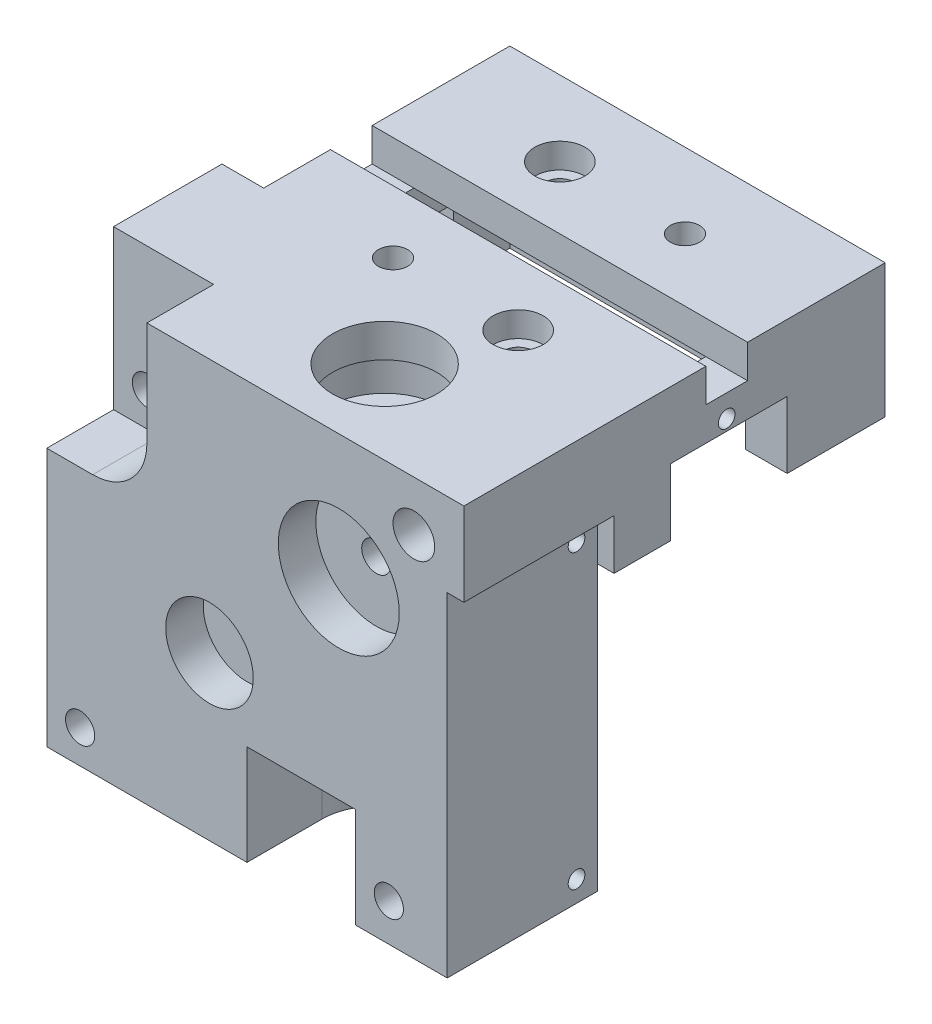
SolidWorks part; units mm, degrees
material "ABS"
ref_plane "Front Plane" through (0, 0, 0) normal (0, 0, 1) x (1, 0, 0)
ref_plane "Top Plane" through (0, 0, 0) normal (0, 1, 0) x (1, 0, 0)
ref_plane "Right Plane" through (0, 0, 0) normal (1, 0, 0) x (0, 0, -1)
sketch "Sketch1" plane through (0, 0, 0) normal (0, 1, 0) x (1, 0, 0)
  line L1 (-17.5, -14) -> (17.5, -14)
  line L2 (-17.5, -14) -> (-17.5, 14)
  line L3 (-17.5, 14) -> (17.5, 14)
  line L4 (17.5, -14) -> (17.5, 14)
  line L5 (-17.5, -14) -> (17.5, 14) construction
  line L6 (-17.5, 14) -> (17.5, -14) construction
  point P0 (0, 0)
  dimension "D1" = 28
  dimension "D2" = 35
extrude "Boss-Extrude1" add sketch "Sketch1" along normal blind 4
sketch "Sketch2" plane through (0, 4, 0) normal (0, 1, 0) x (1, 0, 0)
  line L0 (-17.5, -14) -> (17.5, -14) construction
  line L1 (-17.5, 14) -> (-17.5, -14) construction
  line L2 (-17.5, -14) -> (17.5, -14) construction
  line L3 (17.5, 14) -> (-17.5, 14) construction
  circle A0 centre (-7.5, -10) radius 1.75
  circle A1 centre (-7.5, 10) radius 1.75
  circle A2 centre (7.5, -10) radius 1.75
  circle A3 centre (7.5, 10) radius 1.75
  dimension "D1" = 3.5
  dimension "D2" = 3.5
  dimension "D5" = 3.5
  dimension "D8" = 3.5
  dimension "D3" = 20
  dimension "D4" = 4
  dimension "D6" = 15
  dimension "D7" = 10
  dimension "D9" = 15
  dimension "D10" = 4
  dimension "D11" = 4
extrude "Cut-Extrude1" cut sketch "Sketch2" against normal through all
sketch "Sketch3" plane through (0, 0, 14) normal (0, 0, 1) x (1, 0, 0)
  line L0 (17.5, 4) -> (17.5, 0) construction
  line L1 (-17.5, 4) -> (17.5, 4)
  line L2 (-17.5, 4) -> (-17.5, -46)
  line L3 (-17.5, -46) -> (17.5, -46)
  line L4 (17.5, 4) -> (17.5, -46)
  dimension "D1" = 50
extrude "Boss-Extrude2" add sketch "Sketch3" along normal blind 17.5 and the other way blind 0.5
sketch "Sketch7" plane through (0, 0, -14) normal (0, 0, -1) x (-1, 0, 0)
  line L1 (-17.5, 4) -> (17.5, 4)
  line L2 (-17.5, 4) -> (-17.5, -33)
  line L3 (-17.5, -33) -> (17.5, -33)
  line L4 (17.5, 4) -> (17.5, -33)
  line L6 (17.5, 4) -> (17.5, 0) construction
  dimension "D1" = 37
extrude "Boss-Extrude3" add sketch "Sketch7" along normal blind 5
sketch "Sketch10" plane through (0, 0, -19) normal (0, 0, -1) x (-1, 0, 0)
  line L1 (0, 4) -> (0, -33) construction
  line L3 (17.5, 4) -> (-17.5, 4) construction
  line L4 (-17.5, -33) -> (17.5, -33) construction
  circle A1 centre (-5, -30) radius 1.75
  circle A2 centre (5, -30) radius 1.75
  dimension "D1" = 3
  dimension "D2" = 3.5
  dimension "D4" = 3.5
  dimension "D3" = 5
  dimension "D5" = 5
extrude "Cut-Extrude6" cut sketch "Sketch10" against normal blind 5
sketch "Sketch18" plane through (0, 4, 0) normal (0, 1, 0) x (1, 0, 0)
  line L0 (-17.5, -10) -> (-10.5, -10)
  line L1 (-17.5, 19) -> (-17.5, -31.5) construction
  line L2 (-10.5, -10) -> (-10.5, -11.5)
  line L3 (-10.5, -11.5) -> (-17.5, -11.5)
  line L4 (-17.5, -11.5) -> (-17.5, -10)
  line L5 (17.5, 10) -> (10.5, 10)
  line L6 (17.5, -31.5) -> (17.5, 19) construction
  line L7 (10.5, 10) -> (10.5, 11.5)
  line L8 (10.5, 11.5) -> (17.5, 11.5)
  line L9 (17.5, 11.5) -> (17.5, 10)
  circle A0 centre (-7.5, -10) radius 1.75 construction
  circle A1 centre (7.5, 10) radius 1.75 construction
  dimension "D4" = 3
  dimension "D1" = 0
  dimension "D2" = 3
  dimension "D3" = 1.5
  dimension "D5" = 0
  dimension "D6" = 1.5
extrude "Cut-Extrude14" [suppressed] cut sketch "Sketch18" against normal through all
sketch "Sketch19" plane through (0, 4, 0) normal (0, 1, 0) x (1, 0, 0)
  line L0 (-17.5, 19) -> (-17.5, -31.5) construction
  line L1 (17.5, -31.5) -> (17.5, 19) construction
  circle A0 centre (-7.5, 0) radius 1.75
  circle A1 centre (7.5, 0) radius 1.75
  dimension "D3" = 3.5
  dimension "D4" = 3.5
  dimension "D1" = 10
  dimension "D2" = 10
extrude "Cut-Extrude15" [suppressed] cut sketch "Sketch19" against normal through all
sketch "Sketch20" [suppressed] plane through (0, 0, 0) normal (0, -1, 0) x (1, 0, 0)
  line L1 (10.9641, 0) -> (9.2321, 3)
  line L2 (9.2321, 3) -> (5.7679, 3)
  line L3 (5.7679, 3) -> (4.0359, 0)
  line L4 (4.0359, 0) -> (5.7679, -3)
  line L5 (5.7679, -3) -> (9.2321, -3)
  line L6 (9.2321, -3) -> (10.9641, 0)
  line L7 (-10.9641, 0) -> (-9.2321, -3)
  line L8 (-9.2321, -3) -> (-5.7679, -3)
  line L9 (-5.7679, -3) -> (-4.0359, 0)
  line L10 (-4.0359, 0) -> (-5.7679, 3)
  line L11 (-5.7679, 3) -> (-9.2321, 3)
  line L12 (-9.2321, 3) -> (-10.9641, 0)
  circle A0 centre (7.5, 0) radius 3 construction
  circle A1 centre (-7.5, 0) radius 3 construction
  dimension "D1" = 6
  dimension "D2" = 6
extrude "Cut-Extrude16" [suppressed] cut sketch "Sketch20" against normal blind 3
sketch "Sketch21" [suppressed] plane through (0, 4, 0) normal (0, 1, 0) x (1, 0, 0)
  line L0 (-10.5, -10) -> (-17.5, -10) construction
  circle A0 centre (-17, -10) radius 0.5
  dimension "D1" = 1
extrude "Cut-Extrude17" [suppressed] cut sketch "Sketch21" against normal blind 4
pattern_linear "LPattern2" [suppressed] count 4 spacing 2 of bodies 121
fillet "Fillet2" [suppressed] radius 0.15
sketch "Sketch24" plane through (-17.5, 0, 0) normal (-1, 0, 0) x (0, 0, 1)
  line L5 (31.5, -46) -> (13.5, -46) construction
  line L6 (13.5, -46) -> (31.5, -46)
  line L7 (13.5, -46) -> (13.5, 0)
  line L8 (13.5, 0) -> (31.5, 0)
  line L9 (31.5, -46) -> (31.5, 0)
  line L10 (13.5, 0) -> (13.5, -46) construction
  line L11 (31.5, 4) -> (31.5, -46) construction
extrude "Boss-Extrude4" add sketch "Sketch24" along normal blind 10
sketch "Sketch37" plane through (-17.5, 0, 0) normal (-1, 0, 0) x (0, 0, 1)
  line L1 (10.5, 4) -> (23.5, 4)
  line L2 (10.5, 4) -> (10.5, -10)
  line L3 (10.5, -10) -> (23.5, -10)
  line L4 (23.5, 4) -> (23.5, -10)
  dimension "D1" = 3
  dimension "D2" = 10
  dimension "D3" = 14
extrude "Boss-Extrude9" add sketch "Sketch37" along normal blind 10
sketch "Sketch22" plane through (0, 0, 31.5) normal (0, 0, 1) x (1, 0, 0)
  line L0 (-27.5, -46) -> (-27.5, 0) construction
  line L1 (-15.5, 0) -> (-27.5, 0)
  line L2 (-27.5, -46) -> (17.5, -46) construction
  line L4 (-27.5, 0) -> (-17.5, 0) construction
  line L5 (-27.5, -46) -> (17.5, -46) construction
  line L6 (-27.5, 0) -> (-27.5, -15)
  line L9 (-27.5, -15) -> (-22, -15)
  line L10 (-15.5, 0) -> (-15.5, -8.5)
  line L11 (9.5, -46) -> (-3.5, -46)
  line L12 (9.5, -46) -> (9.5, -34)
  line L13 (9.5, -34) -> (-3.5, -34)
  line L14 (-3.5, -46) -> (-3.5, -34)
  line L16 (-15.5, 0) -> (-17.5, 0)
  line L17 (-15.5, 0) -> (-15.5, 4)
  line L18 (-15.5, 4) -> (-17.5, 4)
  line L19 (-17.5, 0) -> (-17.5, 4)
  circle A0 centre (-23.5, -42) radius 1.75
  circle A1 centre (13.5, -41.5) radius 1.75
  circle A3 centre (7.5, -11) radius 7.25
  circle A4 centre (-8, -26.5) radius 5.25
  arc A5 (-22, -15) -> (-15.5, -8.5) centre (-22, -8.5) ccw
  circle A6 centre (7.5, -11) radius 1.75
  circle A7 centre (-23.5, -11) radius 1.75
  point P21 (-15.5, -15)
  line M3 (-17.5, 4) -> (-17.5, 0)
  line M6 (17.5, 4) -> (-17.5, 4)
  line M24 (-17.5, 0) -> (-27.5, 0)
  line M25 (-27.5, 0) -> (-27.5, -46)
  dimension "D3" = 3.5
  dimension "D6" = 35
  dimension "D7" = 3.5
  dimension "D9" = 14.5
  dimension "D11" = 10.5
  dimension "D15" = 6.5
  dimension "D22" = 3.5
  dimension "D23" = 3.5
  dimension "D2" = 4
  dimension "D4" = 4.5
  dimension "D5" = 4
  dimension "D8" = 12
  dimension "D10" = 35
  dimension "D12" = 19.5
  dimension "D13" = 19.5
  dimension "D14" = 31
  dimension "D16" = 24
  dimension "D17" = 13
  dimension "D18" = 12
  dimension "D19" = 41
  dimension "D20" = 4
  dimension "D21" = 35
extrude "Cut-Extrude19" cut sketch "Sketch22" against normal up to next contours A0 | A1 | A7 | A6 region at (-23.5, -42, 31.5) region at (13.5, -41.5, 31.5) region at (7.5, -11, 31.5) region at (-23.5, -11, 31.5)
extrude "Cut-Extrude20" cut sketch "Sketch22<3>" against normal blind 4.5 contours A3 | A4
sketch "Sketch22<3>" plane through (0, 0, 31.5) normal (0, 0, 1) x (1, 0, 0) same geometry as "Sketch22"
extrude "Cut-Extrude24" cut sketch "Sketch22<5>" against normal blind 8 contours L9 A5 L10 L1 A7 M24 M25 | L1 L17 M6 M3 region at (-21.6364, -6.9513, 31.5) region at (-16.5, 2, 31.5)
sketch "Sketch22<5>" plane through (0, 0, 31.5) normal (0, 0, 1) x (1, 0, 0) same geometry as "Sketch22"
extrude "Cut-Extrude21" cut sketch "Sketch22<4>" against normal blind 15.5 contours L14 L13 L12 L11
sketch "Sketch22<4>" plane through (0, 0, 31.5) normal (0, 0, 1) x (1, 0, 0) same geometry as "Sketch22"
fillet "Fillet3" radius 6.5 2 edges at (9.5, -40, 16) (-3.5, -40, 16)
sketch "Sketch26" plane through (0, -34, 0) normal (0, -1, 0) x (1, 0, 0)
  line L0 (9.5, 31.5) -> (-3.5, 31.5) construction
  line L1 (-3.5, 22.5) -> (-3.5, 31.5) construction
  circle A0 centre (3, 21.5) radius 2.25
  dimension "D1" = 4.5
  dimension "D2" = 10
  dimension "D3" = 6.5
extrude "Cut-Extrude22" cut sketch "Sketch26" against normal through all
sketch "Sketch27" plane through (0, 4, 0) normal (0, 1, 0) x (1, 0, 0)
  circle A0 centre (3, -21.5) radius 6.25
  dimension "D1" = 12.5
extrude "Cut-Extrude23" cut sketch "Sketch27" against normal blind 8
sketch "Sketch41" plane through (-27.5, 0, 0) normal (-1, 0, 0) x (0, 0, 1)
  line L0 (13.5, -10) -> (13.5, -46) construction
  line L1 (13.5, -46) -> (31.5, -46) construction
  line L2 (20.5, -42.5) -> (20.5, -39)
  line L15 (23, -42.5) -> (23, -39)
  line L16 (17, -46) -> (17, -48.5)
  line L17 (20.5, -39) -> (23, -39)
  line L18 (17, -46) -> (21.8734, -46)
  circle A0 centre (17, -42.5) radius 1.25
  arc A1 (17, -46) -> (20.5, -42.5) centre (17, -42.5) ccw
  arc A2 (17, -48.5) -> (23, -42.5) centre (17, -42.5) ccw
  line M16 (13.5, -46) -> (31.5, -46)
  dimension "D5" = 2.5
  dimension "D1" = 3.5
  dimension "D2" = 3.5
  dimension "D3" = 3.5
  dimension "D4" = 2.5
extrude "Boss-Extrude10" [suppressed] add sketch "Sketch41" along normal blind 2.5 contours A0 | A2 L15 L17 L2 A1 M16
sketch "Sketch43" plane through (17.5, 0, 0) normal (1, 0, 0) x (0, 0, -1)
  line L0 (-31.5, -46) -> (-31.5, 4)
  line L1 (-31.5, 4) -> (19, 4)
  line L2 (19, 4) -> (19, -33)
  line L3 (19, -33) -> (14, -33)
  line L6 (-13.5, 0) -> (14, 0) construction
  line L7 (-31.5, -46) -> (-13.5, -46)
  line L11 (-6.75, -4) -> (-6.75, -12)
  line L12 (-6.75, -12) -> (-13.5, -12)
  line L13 (7.25, -4) -> (7.25, -12)
  line L14 (7.25, -12) -> (14, -12)
  line L15 (-6.75, -4) -> (7.25, -4)
  line L16 (-13.5, -12) -> (-13.5, -46)
  line L17 (14, -12) -> (14, -33)
  dimension "D1" = 29
  dimension "D3" = 6.75
  dimension "D4" = 12
  dimension "D5" = 14
extrude "Boss-Extrude11" add sketch "Sketch43" along normal blind 5
sketch "Sketch44" plane through (-17.5, 0, 0) normal (-1, 0, 0) x (0, 0, 1)
  line L0 (10.5, 4) -> (-19, 4)
  line L1 (-19, 4) -> (-19, -33)
  line L2 (-19, -33) -> (-14, -33)
  line L8 (-14, -33) -> (-14, -12)
  line L9 (-14, -12) -> (-7.25, -12)
  line L10 (-7.25, -12) -> (-7.25, -4)
  line L11 (-7.25, -4) -> (6.75, -4)
  line L12 (6.75, -4) -> (6.75, -12)
  line L16 (6.75, -12) -> (13.5, -12)
  line L17 (13.5, -12) -> (13.5, -10)
  line L18 (13.5, -10) -> (10.5, -10)
  line L19 (10.5, -10) -> (10.5, 4)
extrude "Boss-Extrude12" add sketch "Sketch44" along normal blind 5
sketch "Sketch29" plane through (0, 0, 13.5) normal (0, 0, -1) x (-1, 0, 0)
  circle A0 centre (-7.5, -11) radius 2.5
  circle A2 centre (23.5, -42) radius 2.5
  circle A3 centre (23.5, -11) radius 2.5
  dimension "D1" = 5
  dimension "D3" = 5
  dimension "D4" = 5
extrude "Cut-Extrude25" cut sketch "Sketch29" against normal blind 5 and the other way up to surface (6.75 mm away) other way up to face at (-20, -8, 6.75)
sketch "Sketch55" plane through (0, 0, 13.5) normal (0, 0, -1) x (-1, 0, 0)
  circle A0 centre (-13.5, -41.5) radius 2.75
  dimension "D1" = 5.5
extrude "Cut-Extrude42" cut sketch "Sketch55" against normal blind 10
sketch "Sketch30" plane through (0, 4, 0) normal (0, 1, 0) x (1, 0, 0)
  circle A0 centre (-7.5, 10) radius 3
  circle A2 centre (7.5, -10) radius 3
  dimension "D1" = 6
  dimension "D3" = 6
extrude "Cut-Extrude26" cut sketch "Sketch30" against normal blind 3
ref_plane "Plane1" [suppressed] through (0, 0, 0) normal (-1, 0, 0) x (0, 0, 1)
sketch "Sketch38" plane through (0, -4, 0) normal (0, 1, 0) x (1, 0, 0)
  circle A0 centre (3, -21.5) radius 7
  dimension "D1" = 14
extrude "Cut-Extrude31" cut sketch "Sketch38" along normal blind 4
sketch "Sketch39" plane through (-27.5, 0, 0) normal (-1, 0, 0) x (0, 0, 1)
  line L0 (13.5, -46) -> (17, -46)
  line L1 (13.5, -46) -> (31.5, -46) construction
  line L2 (13.5, -46) -> (13.5, -19)
  line L3 (13.5, -10) -> (13.5, -46) construction
  line L4 (13.5, -19) -> (17, -19)
  line L5 (20.5, -22.5) -> (20.5, -26)
  line L6 (20.5, -26) -> (27.5, -26)
  line L7 (27.5, -26) -> (27.5, -39)
  line L8 (27.5, -39) -> (20.5, -39)
  line L9 (20.5, -39) -> (20.5, -42.5)
  line L11 (27.5, -29) -> (23.5, -29)
  line L12 (27.5, -29) -> (27.5, -36)
  line L13 (27.5, -36) -> (23.5, -36)
  line L14 (23.5, -29) -> (23.5, -36)
  line L15 (13.5, -26) -> (18.5, -26)
  line L16 (13.5, -26) -> (13.5, -39)
  line L17 (13.5, -39) -> (18.5, -39)
  line L18 (18.5, -26) -> (18.5, -39)
  arc A0 (17, -46) -> (20.5, -42.5) centre (17, -42.5) ccw
  arc A1 (17, -19) -> (20.5, -22.5) centre (17, -22.5) cw
  point P15 (20.5, -46)
  point P18 (20.5, -19)
  dimension "D7" = 3.5
  dimension "D1" = 7
  dimension "D2" = 27
  dimension "D3" = 7
  dimension "D4" = 7
  dimension "D5" = 7
  dimension "D6" = 13
  dimension "D8" = 4
  dimension "D9" = 7
  dimension "D10" = 3
  dimension "D11" = 5
extrude "Cut-Extrude32" cut sketch "Sketch39" against normal blind 3 contours L18 L15 L2 L17 | L11 L14 L13 L7 region at (-27.5, -32.5, 16) region at (-27.5, -32.5, 25.5)
sketch "Sketch40" plane through (-27.5, 0, 0) normal (-1, 0, 0) x (0, 0, 1)
  line L0 (13.5, -10) -> (13.5, -26) construction
  line L1 (13.5, -46) -> (31.5, -46) construction
  circle A0 centre (17, -22.5) radius 1.75
  dimension "D3" = 3.5
  dimension "D1" = 3.5
  dimension "D2" = 23.5
extrude "Cut-Extrude33" cut sketch "Sketch40" against normal blind 15
sketch "Sketch51" plane through (-27.5, 0, 0) normal (-1, 0, 0) x (0, 0, 1)
  circle A0 centre (17, -22.5) radius 2.5
  dimension "D1" = 5
extrude "Cut-Extrude38" cut sketch "Sketch51" against normal blind 4
sketch "Sketch42" plane through (0, 0, 31.5) normal (0, 0, 1) x (1, 0, 0)
  circle A0 centre (16.5, -2) radius 1.4
  circle A1 centre (-23.5, -42) radius 1.75 construction
  dimension "D3" = 2.8
  dimension "D1" = 40
  dimension "D2" = 40
extrude "Cut-Extrude34" cut sketch "Sketch42" against normal blind 10
sketch "Sketch45" plane through (22.5, 0, 0) normal (1, 0, 0) x (0, 0, -1)
  line L0 (-13.5, 0) -> (14, 0) construction
  circle A0 centre (0, -2.7) radius 1
  dimension "D2" = 2
  dimension "D1" = 2.7
extrude "Cut-Extrude35" cut sketch "Sketch45" against normal through all
sketch "Sketch46" plane through (-27.5, 0, 0) normal (-1, 0, 0) x (0, 0, 1)
  line L0 (13.5, -39) -> (13.5, -46) construction
  line L1 (13.5, -46) -> (31.5, -46) construction
  circle A0 centre (17, -42.5) radius 1.5
  dimension "D3" = 3
  dimension "D1" = 3.5
  dimension "D2" = 3.5
extrude "Boss-Extrude13" add sketch "Sketch46" along normal blind 2.5
sketch "Sketch48" plane through (22.5, 0, 0) normal (1, 0, 0) x (0, 0, -1)
  line L0 (-31.5, 4) -> (-31.5, -46) construction
  line L1 (-13.5, -46) -> (-31.5, -46)
  line L2 (-13.5, -46) -> (-13.5, -6)
  line L3 (-13.5, -6) -> (-31.5, -6)
  line L4 (-31.5, -46) -> (-31.5, -6)
  dimension "D1" = 40
extrude "Cut-Extrude36" cut sketch "Sketch48" against normal blind 2
sketch "Sketch49" plane through (20.5, 0, 0) normal (1, 0, 0) x (0, 0, -1)
  line L0 (-31.5, -46) -> (-13.5, -46) construction
  line L1 (-13.5, -46) -> (-13.5, -12) construction
  circle A0 centre (-16, -43.5) radius 1
  circle A1 centre (-16, -8.5) radius 1
  dimension "D3" = 2
  dimension "D5" = 2
  dimension "D1" = 2.5
  dimension "D2" = 2.5
  dimension "D4" = 35
extrude "Cut-Extrude37" cut sketch "Sketch49" against normal blind 10
sketch "Sketch53" plane through (0, 4, 0) normal (0, 1, 0) x (1, 0, 0)
  line L0 (22.5, 19) -> (22.5, -31.5) construction
  line L1 (-22.5, 2.5) -> (22.5, 2.5)
  line L2 (-22.5, 2.5) -> (-22.5, -2.5)
  line L3 (-22.5, -2.5) -> (22.5, -2.5)
  line L4 (22.5, 2.5) -> (22.5, -2.5)
  line L5 (-22.5, 2.5) -> (22.5, -2.5) construction
  line L6 (-22.5, -2.5) -> (22.5, 2.5) construction
  point P0 (0, 0)
  dimension "D1" = 5
extrude "Cut-Extrude40" cut sketch "Sketch53" against normal up to surface (4 mm away) up to face at (-7.5, 0, -8.25)
sketch "Sketch54" plane through (-22.5, 0, 0) normal (-1, 0, 0) x (0, 0, 1)
  line L1 (-14, -12) -> (-19, -12)
  line L2 (-14, -12) -> (-14, -33)
  line L3 (-14, -33) -> (-19, -33)
  line L4 (-19, -12) -> (-19, -33)
extrude "Cut-Extrude41" cut sketch "Sketch54" against normal through all
sketch "Sketch56" plane through (0, 0, 31.5) normal (0, 0, 1) x (1, 0, 0)
  circle A0 centre (16.5, -2) radius 2.5
  dimension "D1" = 5
extrude "Cut-Extrude43" cut sketch "Sketch56" against normal blind 8
